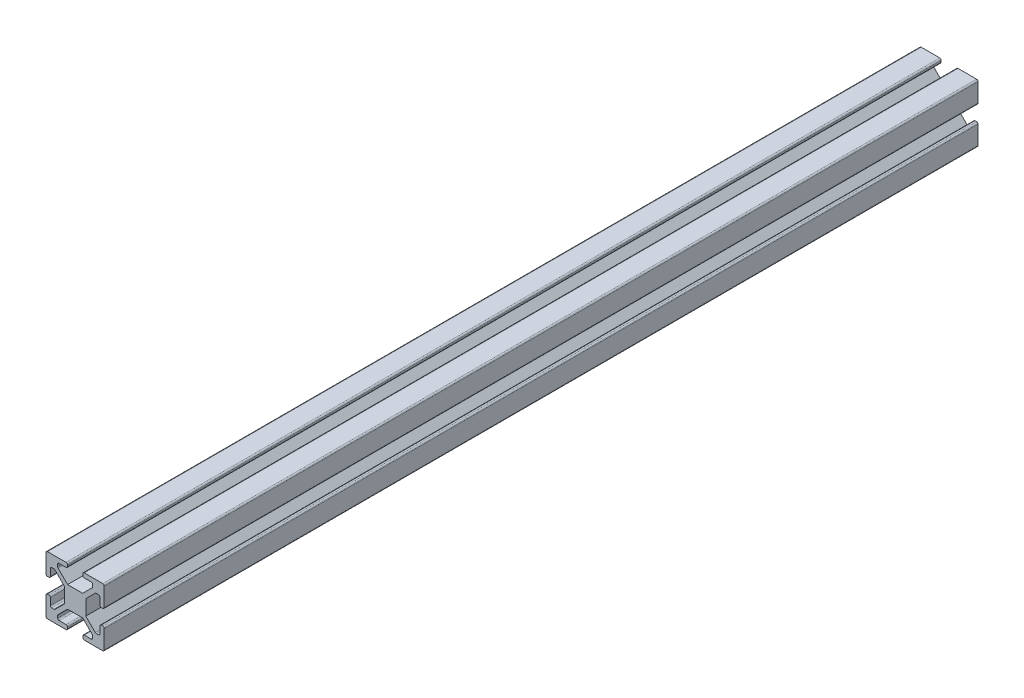
SolidWorks part; units mm, degrees
material "6061 Alloy"
ref_plane "Front Plane" through (0, 0, 0) normal (0, 0, 1) x (1, 0, 0)
ref_plane "Top Plane" through (0, 0, 0) normal (0, 1, 0) x (1, 0, 0)
ref_plane "Right Plane" through (0, 0, 0) normal (1, 0, 0) x (0, 0, -1)
sketch "Sketch1" plane through (0, 0, 0) normal (0, 0, 1) x (1, 0, 0)
  line L0 (-10, 2.63) -> (-10, 10)
  line L1 (-10, 10) -> (-2.63, 10)
  line L2 (-2.63, 10) -> (-2.63, 8.5)
  line L3 (-2.63, 8.5) -> (-5.995, 8.5)
  line L4 (-5.995, 8.5) -> (-5.995, 7.0557)
  line L5 (-5.995, 7.0557) -> (-2.5943, 3.655)
  line L6 (-2.5943, 3.655) -> (2.5943, 3.655)
  line L7 (0, 3.655) -> (0, 0) construction
  line L8 (0, 0) -> (-3.655, 0) construction
  line L9 (-3.655, -2.5943) -> (-3.655, 2.5943)
  line L10 (-3.655, 2.5943) -> (-7.0557, 5.995)
  line L11 (-7.0557, 5.995) -> (-8.5, 5.995)
  line L12 (-8.5, 5.995) -> (-8.5, 2.63)
  line L13 (-8.5, 2.63) -> (-10, 2.63)
  line L14 (8.5, 2.63) -> (10, 2.63)
  line L15 (8.5, 5.995) -> (8.5, 2.63)
  line L16 (7.0557, 5.995) -> (8.5, 5.995)
  line L17 (3.655, 2.5943) -> (7.0557, 5.995)
  line L18 (3.655, -2.5943) -> (3.655, 2.5943)
  line L19 (5.995, 7.0557) -> (2.5943, 3.655)
  line L20 (5.995, 8.5) -> (5.995, 7.0557)
  line L21 (2.63, 8.5) -> (5.995, 8.5)
  line L22 (2.63, 10) -> (2.63, 8.5)
  line L23 (10, 10) -> (2.63, 10)
  line L24 (10, 2.63) -> (10, 10)
  line L25 (10, -2.63) -> (10, -10)
  line L26 (10, -10) -> (2.63, -10)
  line L27 (2.63, -10) -> (2.63, -8.5)
  line L28 (2.63, -8.5) -> (5.995, -8.5)
  line L29 (5.995, -8.5) -> (5.995, -7.0557)
  line L30 (5.995, -7.0557) -> (2.5943, -3.655)
  line L31 (3.655, -2.5943) -> (7.0557, -5.995)
  line L32 (7.0557, -5.995) -> (8.5, -5.995)
  line L33 (8.5, -5.995) -> (8.5, -2.63)
  line L34 (8.5, -2.63) -> (10, -2.63)
  line L35 (-8.5, -2.63) -> (-10, -2.63)
  line L36 (-8.5, -5.995) -> (-8.5, -2.63)
  line L37 (-7.0557, -5.995) -> (-8.5, -5.995)
  line L38 (-3.655, -2.5943) -> (-7.0557, -5.995)
  line L39 (-2.5943, -3.655) -> (2.5943, -3.655)
  line L40 (-5.995, -7.0557) -> (-2.5943, -3.655)
  line L41 (-5.995, -8.5) -> (-5.995, -7.0557)
  line L42 (-2.63, -8.5) -> (-5.995, -8.5)
  line L43 (-2.63, -10) -> (-2.63, -8.5)
  line L44 (-10, -10) -> (-2.63, -10)
  line L45 (-10, -2.63) -> (-10, -10)
  point P2 (-3.2821, 3.2821)
  point P16 (0, 0)
  point P17 (0, 0)
  point P18 (-3.6841, 4.4522)
  point P19 (-8.293, 6.9843)
  point P20 (-12.8166, 10)
  point P41 (3.655, 0)
  dimension "D1" = 20
  dimension "D2" = 20
  dimension "D3" = 5.26
  dimension "D4" = 11.99
  dimension "D5" = 1.5
  dimension "D6" = 1.5
  dimension "D7" = 7.31
extrude "Boss-Extrude1" add sketch "Sketch1" against normal blind 300
fillet "Fillet1" radius 0.5 36 edges at (10, 10, -150) (7.0557, 5.995, -150) (8.5, 2.63, -150) (10, 2.63, -150) (8.5, 5.995, -150) (2.63, 10, -150) (2.63, 8.5, -150) (5.995, 8.5, -150) (5.995, 7.0557, -150) (10, -10, -150) (10, -2.63, -150) (8.5, -2.63, -150) (8.5, -5.995, -150) (7.0557, -5.995, -150) (5.995, -7.0557, -150) (5.995, -8.5, -150) (2.63, -8.5, -150) (2.63, -10, -150) (-10, -10, -150) (-2.63, -10, -150) (-2.63, -8.5, -150) (-5.995, -8.5, -150) (-5.995, -7.0557, -150) (-7.0557, -5.995, -150) (-8.5, -5.995, -150) (-10, -2.63, -150) (-8.5, -2.63, -150) (-7.0557, 5.995, -150) (-10, 10, -150) (-10, 2.63, -150) (-8.5, 2.63, -150) (-8.5, 5.995, -150) (-5.995, 8.5, -150) (-5.995, 7.0557, -150) (-2.63, 8.5, -150) (-2.63, 10, -150)
